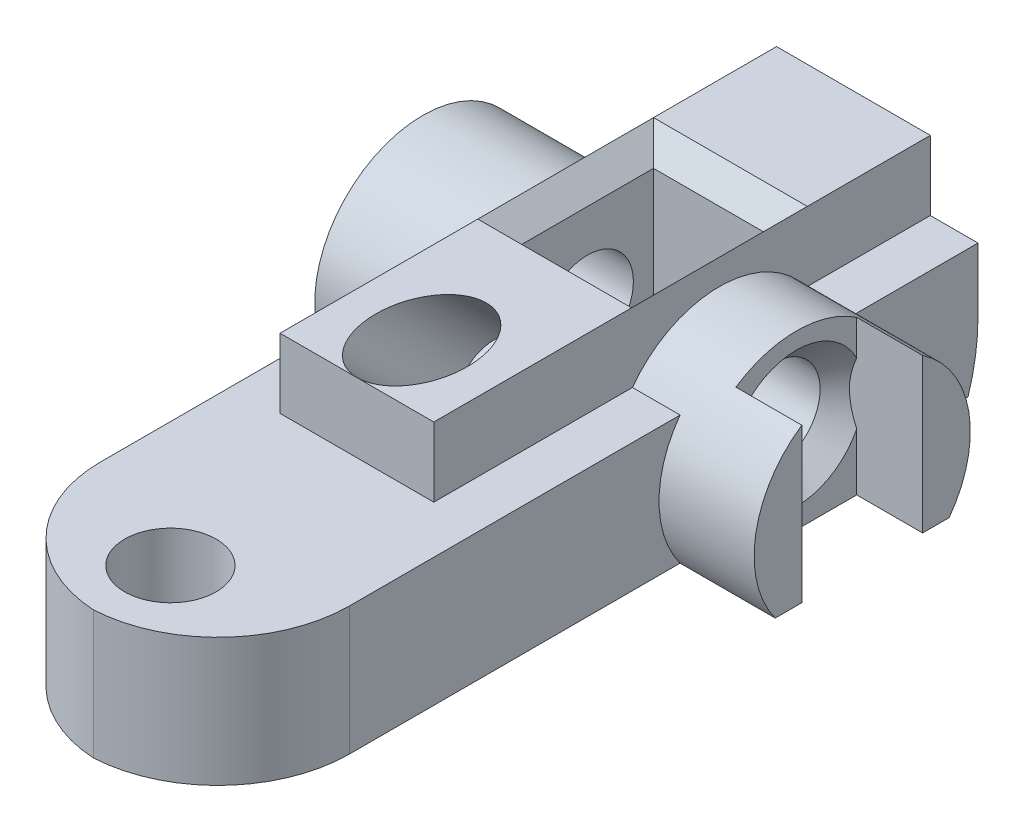
SolidWorks part; units mm, degrees
ref_plane "Front Plane" through (0, 0, 0) normal (0, 0, 1) x (1, 0, 0)
ref_plane "Top Plane" through (0, 0, 0) normal (0, 1, 0) x (1, 0, 0)
ref_plane "Right Plane" through (0, 0, 0) normal (1, 0, 0) x (0, 0, -1)
sketch "Sketch2" plane through (0, 0, 0) normal (1, 0, 0) x (0, 0, -1)
  line L0 (0, 4.92) -> (0, 2.92) construction
  line L1 (0, -4.92) -> (0, -2.92) construction
  line L2 (3.9598, -2.92) -> (-3.9598, -2.92)
  line L3 (3.9598, 2.92) -> (-3.9598, 2.92) construction
  circle A0 centre (0, 0) radius 4.92 construction
  arc A1 (-3.9598, 2.92) -> (-3.9598, -2.92) centre (0, 0) ccw
  arc A2 (3.9598, 2.92) -> (3.9598, -2.92) centre (0, 0) cw
  arc A3 (-3.9598, 2.92) -> (3.9598, 2.92) centre (0, 0) cw
  point P10 (0, -2.92)
  point P12 (0, 2.92)
  dimension "D1" = 9.84
  dimension "D2" = 2
extrude "Boss-Extrude1" add sketch "Sketch2" along normal blind 20 contours A2 L3 A1 L2 region at (0, 0.6371, 0)
sketch "Sketch3" plane through (0, 0, 0) normal (0, 0, 1) x (1, 0, 0)
  line L0 (10, 2.92) -> (10, -2.92) construction
  line L2 (20, -2.92) -> (0, -2.92) construction
  line L3 (0, 2.92) -> (20, 2.92) construction
  line L4 (4.33, -2.92) -> (15.67, -2.92)
  line L5 (4.33, -2.92) -> (4.33, 2.92)
  line L6 (4.33, 2.92) -> (15.67, 2.92)
  line L7 (15.67, -2.92) -> (15.67, 2.92)
  line L8 (4.33, -2.92) -> (15.67, 2.92) construction
  line L9 (4.33, 2.92) -> (15.67, -2.92) construction
  line L10 (0, 4.92) -> (0, -2.92) construction
  line L11 (20, -2.92) -> (20, 4.92) construction
  point P6 (10, 0)
  dimension "D1" = 11.34
  dimension "D2" = 5.84
extrude "Boss-Extrude2" add sketch "Sketch3" along normal blind 25
fillet "Fillet1" radius 6 2 edges at (15.67, 0, 25) (4.33, 0, 25)
sketch "Sketch4" plane through (0, -2.92, 0) normal (0, -1, 0) x (1, 0, 0)
  line L0 (10, 7) -> (10, -3.9598) construction
  line L1 (20, -3.9598) -> (0, -3.9598) construction
  line L3 (13.5, 4.0402) -> (6.5, 4.0402)
  line L4 (13.5, 4.0402) -> (13.5, -3.9598)
  line L5 (13.5, -3.9598) -> (6.5, -3.9598)
  line L6 (6.5, 4.0402) -> (6.5, -3.9598)
  line L7 (13.5, 4.0402) -> (6.5, -3.9598) construction
  line L8 (13.5, -3.9598) -> (6.5, 4.0402) construction
  point P5 (10, 0.0402)
  dimension "D1" = 7
  dimension "D2" = 8
extrude "Boss-Extrude3" add sketch "Sketch4" against normal blind 9
sketch "Sketch10" plane through (0, 0, 0) normal (0, 0, 1) x (1, 0, 0)
  line L6 (10, -2.92) -> (15.67, -2.92) construction
  line L7 (15.67, -2.92) -> (15.67, 2.92) construction
  line L9 (4.33, 2.92) -> (4.33, -2.92) construction
  line L10 (4.33, -2.92) -> (10, -2.92) construction
  line L12 (10, -2.92) -> (15.67, -2.92)
  line L13 (15.67, -2.92) -> (15.67, 2.92)
  line L14 (15.67, 2.92) -> (13.5, 2.92)
  line L15 (4.33, 2.92) -> (4.33, -2.92)
  line L16 (4.33, -2.92) -> (10, -2.92)
  line L17 (6.5, 2.92) -> (4.33, 2.92)
  line L22 (6.5, 2.92) -> (13.5, 2.92)
  line L23 (13.5, 2.92) -> (13.5, 6.08)
  line L24 (13.5, 6.08) -> (6.5, 6.08)
  line L25 (6.5, 6.08) -> (6.5, 2.92)
  line L27 (13.5, 2.92) -> (13.5, 6.08)
  line L28 (13.5, 6.08) -> (6.5, 6.08)
  line L29 (6.5, 6.08) -> (6.5, 2.92)
  line L30 (6.5, 2.92) -> (13.5, 2.92)
  dimension "D1" = 0
extrude "Boss-Extrude4" add sketch "Sketch10" against normal blind 9.6 and the other way blind 13 contours L29 L30 L27 L28 | L30 L17 L15 L16 L12 L13 L14 region at (10, 0, 0) region at (10, 4.5, 0)
sketch "Sketch5" plane through (0, 6.08, 0) normal (0, 1, 0) x (1, 0, 0)
  line L0 (10, -3.9598) -> (10, 3.9598) construction
  line L4 (7.5, -3) -> (12.5, -3)
  line L5 (7.5, -3) -> (7.5, 3)
  line L6 (7.5, 3) -> (12.5, 3)
  line L7 (12.5, -3) -> (12.5, 3)
  line L8 (7.5, -3) -> (12.5, 3) construction
  line L9 (7.5, 3) -> (12.5, -3) construction
  line L10 (6.5, 3.9598) -> (13.5, 3.9598) construction
  line L11 (6.5, 3.9598) -> (6.5, 9.6) construction
  line L12 (13.5, 9.6) -> (13.5, -13) construction
  line L15 (6.5, -3.9598) -> (13.5, -3.9598) construction
  line L16 (6.5, 3.9598) -> (6.5, 9.6) construction
  line L17 (13.5, 9.6) -> (13.5, -13) construction
  line L19 (13.5, -3.9598) -> (15.67, -3.9598) construction
  line L20 (13.5, 3.9598) -> (15.67, 3.9598) construction
  point P6 (10, 0)
  point P12 (10, -3.9598)
  dimension "D1" = 6
  dimension "D2" = 5
extrude "Cut-Extrude1" cut sketch "Sketch5" against normal up to surface (9 mm away) up to face at (10, -2.92, 3.5422)
sketch "Sketch6" plane through (0, 2.92, 0) normal (0, 1, 0) x (1, 0, 0)
  line L0 (10, -21.4909) -> (10, -24.9909) construction
  circle A0 centre (10, -21.4909) radius 2.0825
  dimension "D1" = 4.165
  dimension "D2" = 3.5
extrude "Cut-Extrude2" cut sketch "Sketch6" against normal up to surface (5.84 mm away) up to face at (10, -2.92, 0)
sketch "Sketch8" plane through (20, 0, 0) normal (1, 0, 0) x (0, 0, -1)
  line L1 (-3, -2.92) -> (3, -2.92) construction
  line L2 (-3, -2.92) -> (3, -2.92) construction
  line L3 (0, -2.92) -> (0, 1.08) construction
  circle A0 centre (0, 1.08) radius 2.0825
  dimension "D2" = 4.165
  dimension "D1" = 4
extrude "Cut-Extrude3" cut sketch "Sketch8" against normal up to surface (20 mm away) up to face at (0, 1, 0)
sketch "Sketch9" plane through (0, -2.92, 0) normal (0, 1, 0) x (1, 0, 0)
  line L0 (20, -2.0825) -> (20, 2.0825) construction
  line L1 (20, -2.0825) -> (20, 2.0825) construction
  line L2 (20, -2.75) -> (20, 2.75)
  line L4 (20, 2.75) -> (17, 2.75)
  line L5 (17, 2.75) -> (17, -2.75)
  line L6 (17, -2.75) -> (20, -2.75)
  line L7 (20, -2.0825) -> (20, 2.0825)
  point P7 (20, 0)
  line M46 (20, 3.9598) -> (20, -3.9598)
  dimension "D1" = 3
  dimension "D2" = 5.5
extrude "Cut-Extrude4" cut sketch "Sketch9" along normal up to surface (6.9997 mm away) contours L6 L5 L4 L2 M46 region at (18.5, -2.92, 0) up to face at (16.21, 1.23, 0)
chamfer "Chamfer1" distance 1 angle 45 6 edges at (10, 6.08, 3) (7.5, 6.08, 0) (10, 6.08, -3) (12.5, 6.08, 0) (0, 1.08, -2.0825) (17, 1.08, -2.0825)
sketch "Sketch11" plane through (4.33, 0, 0) normal (-1, 0, 0) x (0, 0, 1)
  line L1 (-9.6, -2.92) -> (-3.9598, -2.92) construction
  line L2 (-9.1451, -2.92) -> (-9.6, -2.92)
  line L3 (-9.6, -2.92) -> (-9.6, 0)
  line L4 (-9.6, 2.92) -> (-9.6, -2.92) construction
  arc A0 (-9.6, 0) -> (-9.1451, -2.92) centre (0, 0) ccw
extrude "Cut-Extrude5" cut sketch "Sketch11" against normal up to surface (11.34 mm away) up to face at (15.67, 0, -7.0199)
ref_plane "Plane1" through (0, 9.54, 9.54) normal (0, 0.7071, 0.7071) x (-1, 0, 0)
sketch "Sketch13" plane through (0, 9.54, 9.54) normal (0, 0.7071, 0.7071) x (-1, 0, 0)
  line L1 (-13.5, 4.8932) -> (-6.5, 4.8932) construction
  line L2 (-10, 4.8932) -> (-10, 2.8107) construction
  line L4 (-13.5, 4.8932) -> (-6.5, 4.8932) construction
  line L5 (-6.5, 7.1276) -> (-6.5, 0.7352) construction
  circle A0 centre (-10, 2.8107) radius 2.0825
  dimension "D1" = 4.165
extrude "Cut-Extrude7" cut sketch "Sketch13" against normal blind 8
sketch "Sketch14" plane through (0, -2.92, 0) normal (0, -1, 0) x (1, 0, 0)
  line L0 (12.5, 3) -> (12.5, -3) construction
  line L1 (12.5, -3) -> (7.5, -3) construction
  line L2 (7.5, -3) -> (7.5, 3) construction
  line L3 (7.5, 3) -> (12.5, 3) construction
  line L4 (12.5, 3) -> (12.5, -3)
  line L5 (12.5, -3) -> (7.5, -3)
  line L6 (7.5, -3) -> (7.5, 3)
  line L7 (7.5, 3) -> (12.5, 3)
extrude "Boss-Extrude5" add sketch "Sketch14" against normal blind 1
